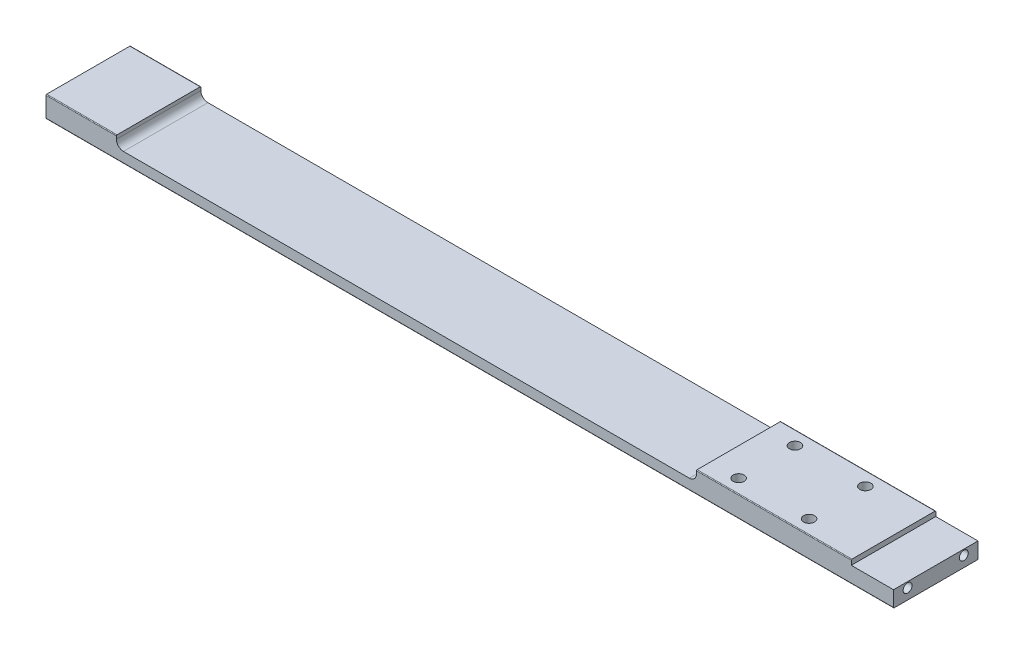
SolidWorks part; units mm, degrees
ref_plane "Front Plane" through (0, 0, 0) normal (0, 0, 1) x (1, 0, 0)
ref_plane "Top Plane" through (0, 0, 0) normal (0, 1, 0) x (1, 0, 0)
ref_plane "Right Plane" through (0, 0, 0) normal (1, 0, 0) x (0, 0, -1)
sketch "Sketch1" plane through (0, 0, 0) normal (0, 1, 0) x (1, 0, 0)
  line L1 (191.135, -19.05) -> (-191.135, -19.05)
  line L2 (191.135, -19.05) -> (191.135, 19.05)
  line L3 (191.135, 19.05) -> (-191.135, 19.05)
  line L4 (-191.135, -19.05) -> (-191.135, 19.05)
  line L5 (191.135, -19.05) -> (-191.135, 19.05) construction
  line L6 (191.135, 19.05) -> (-191.135, -19.05) construction
  point P0 (0, 0)
  dimension "Length" = 382.27
  dimension "Width" = 38.1
sketch "Sketch2" plane through (0, 0, 0) normal (1, 0, 0) x (0, 0, -1)
  line L0 (19.05, 4.7625) -> (19.05, -4.7625) construction
  point P2 (19.05, 0)
  dimension "Thickness" = 9.525
sketch "Sketch3" plane through (0, 0, 0) normal (0, 1, 0) x (1, 0, 0)
  line L1 (-191.135, 19.05) -> (191.135, 19.05)
  line L2 (-191.135, 19.05) -> (-191.135, -19.05)
  line L3 (-191.135, -19.05) -> (191.135, -19.05)
  line L4 (191.135, 19.05) -> (191.135, -19.05)
extrude "Boss-Extrude1" add sketch "Sketch3" against normal up to vertex (4.7625 mm away) and the other way up to vertex (4.7625 mm away) up to point (0, -4.7625, -19.05) other way up to point (0, 4.7625, -19.05)
fillet "Fillet1" radius 0.3143 4 edges at (0, -4.7625, 19.05) (0, -4.7625, -19.05) (0, 4.7625, -19.05) (0, 4.7625, 19.05)
sketch "Sketch4" plane through (-191.135, 0, 0) normal (-1, 0, 0) x (0, 0, 1)
  line L0 (0, 0) -> (12.7, 0) construction
  line L1 (0, 0) -> (-12.6447, 0) construction
hole_wizard "Tap Drill for #10-32 Tap1" positions "Sketch5" profile "Sketch6" hole size "#10-32" standard "ANSI Inch"
sketch "Sketch5" plane through (-191.135, 0, 0) normal (-1, 0, 0) x (0, 0, 1)
  point P0 (-12.6447, 0)
  point P3 (12.7, 0)
sketch "Sketch6" plane through (-191.135, 0, -12.6447) normal (0, 1, 0) x (0, 0, 1)
  line L0 (0, 0) -> (0, 26.6133)
  line L1 (0, 26.6133) -> (2.0193, 25.4)
  line L2 (2.0193, 25.4) -> (2.0193, 0)
  line L5 (2.0193, 0) -> (0, 0)
  line L10 (0, 26.6133) -> (-2.0193, 25.4) construction
  line L11 (0, -6.35) -> (0, 107.95) construction
  dimension "Hole Dia." = 4.0386
  dimension "Hole Depth" = 25.4
  dimension "Drill Angle" = 118
hole_wizard "Tap Drill for #10-32 Tap2" positions "Sketch7" profile "Sketch8" hole size "#10-32" standard "ANSI Inch"
sketch "Sketch7" plane through (191.135, 0, 0) normal (1, 0, 0) x (0, 0, -1)
  point P0 (-12.7, 0)
  point P3 (12.6447, 0)
sketch "Sketch8" plane through (191.135, 0, 12.7) normal (0, 1, 0) x (0, 0, -1)
  line L0 (0, 0) -> (0, 26.6133)
  line L1 (0, 26.6133) -> (2.0193, 25.4)
  line L2 (2.0193, 25.4) -> (2.0193, 0)
  line L5 (2.0193, 0) -> (0, 0)
  line L10 (0, 26.6133) -> (-2.0193, 25.4) construction
  line L11 (0, -6.35) -> (0, 107.95) construction
  dimension "Hole Dia." = 4.0386
  dimension "Hole Depth" = 25.4
  dimension "Drill Angle" = 118
sketch "Sketch10" plane through (0, 0, -19.05) normal (0, 0, -1) x (-1, 0, 0)
  line L0 (159.385, 4.7625) -> (159.385, 3.175)
  line L1 (-191.135, 4.7625) -> (191.135, 4.7625) construction
  line L2 (156.21, 0) -> (-99.06, 0)
  line L3 (-102.235, 3.175) -> (-102.235, 4.7625)
  line L4 (-102.235, 4.7625) -> (159.385, 4.7625)
  line L5 (-191.135, -4.7625) -> (-191.135, 78.7988) construction
  line L6 (191.135, -4.7625) -> (191.135, 78.7988) construction
  line L7 (-191.135, 4.7625) -> (-172.085, 4.7625)
  line L8 (-172.085, 4.7625) -> (-172.085, 2.4765)
  line L9 (-172.085, 2.4765) -> (-191.135, 2.4765)
  line L10 (-191.135, -4.4482) -> (-191.135, 4.4482) construction
  line L11 (-191.135, 2.4765) -> (-191.135, 4.7625)
  arc A0 (159.385, 3.175) -> (156.21, 0) centre (156.21, 3.175) cw
  arc A1 (-99.06, 0) -> (-102.235, 3.175) centre (-99.06, 3.175) cw
  point P12 (159.385, 0)
  dimension "D4" = 3.175
  dimension "D1" = 88.9
  dimension "D2" = 31.75
  dimension "D3" = 4.7625
  dimension "D5" = 19.05
  dimension "D6" = 2.286
extrude "Cut-Extrude1" cut sketch "Sketch10" against normal through all
sketch "Sketch13" plane through (0, -4.7625, 0) normal (0, -1, 0) x (1, 0, 0)
  line L0 (191.135, 0) -> (146.685, 0) construction
  line L1 (191.135, 18.7357) -> (191.135, -18.7357) construction
  line L2 (146.685, 0) -> (146.685, 12.7) construction
  line L3 (146.685, 12.7) -> (114.935, 12.7) construction
  line L4 (114.935, 12.7) -> (114.935, -12.7) construction
  line L5 (114.935, -12.7) -> (146.685, -12.7) construction
  line L6 (146.685, -12.7) -> (146.685, 0) construction
  dimension "D1" = 44.45
  dimension "D2" = 31.75
  dimension "D3" = 31.75
hole_wizard "#10 Clearance Hole1" positions "Sketch14" profile "Sketch15" hole size "#10" standard "ANSI Inch" end condition through all
sketch "Sketch14" plane through (0, -4.7625, 0) normal (0, -1, 0) x (-1, 0, 0)
  point P0 (-114.935, 12.7)
  point P3 (-146.685, 12.7)
  point P6 (-146.685, -12.7)
  point P9 (-114.935, -12.7)
sketch "Sketch15" plane through (114.935, -4.7625, -12.7) normal (1, 0, 0) x (0, 0, -1)
  line L0 (0, 0) -> (0, 9.525)
  line L1 (0, 9.525) -> (2.4892, 9.525)
  line L2 (2.4892, 9.525) -> (2.4892, 3.1411)
  line L3 (2.4892, 3.1411) -> (5.2197, 0)
  line L5 (5.2197, 0) -> (0, 0)
  line L6 (-2.4892, 3.1411) -> (-5.2197, 0) construction
  line L11 (0, -6.35) -> (0, 107.95) construction
  dimension "Thru Hole Dia." = 4.9784
  dimension "Thru Hole Depth" = 9.525
  dimension "Near C'Sink Dia." = 10.4394
  dimension "Near C'Sink Angle" = 82
equation "\"D1@Fillet1\" = \"Thickness@Sketch2\" * .033"
